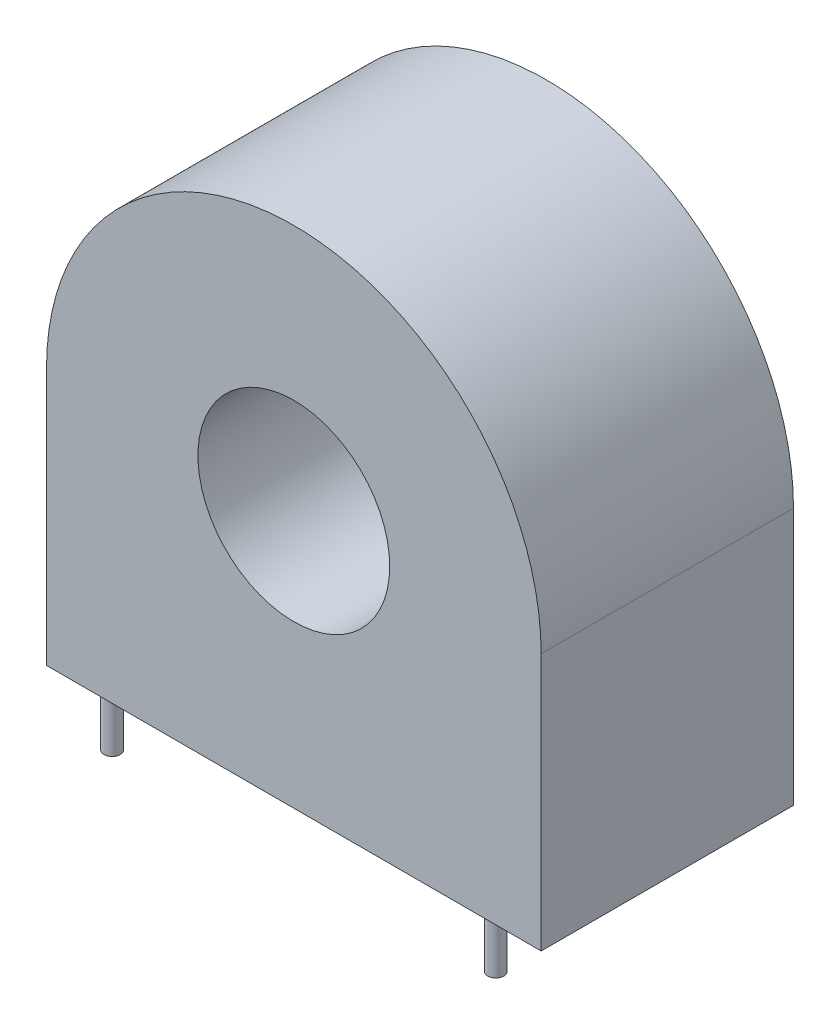
SolidWorks part; units mm, degrees
ref_plane "Front" through (0, 0, 0) normal (0, 0, 1) x (1, 0, 0)
ref_plane "Top" through (0, 0, 0) normal (0, 1, 0) x (1, 0, 0)
ref_plane "Right" through (0, 0, 0) normal (1, 0, 0) x (0, 0, -1)
sketch "Эскиз1" plane through (0, 0, 0) normal (0, 0, 1) x (1, 0, 0)
  line L1 (12.25, -6.375) -> (-12.25, -6.375)
  line L2 (12.25, -6.375) -> (12.25, 6.375)
  line L3 (12.25, 6.375) -> (-12.25, 6.375) construction
  line L4 (-12.25, -6.375) -> (-12.25, 6.375)
  line L5 (12.25, -6.375) -> (-12.25, 6.375) construction
  line L6 (12.25, 6.375) -> (-12.25, -6.375) construction
  arc A0 (12.25, 6.375) -> (-12.25, 6.375) centre (0, 6.375) ccw
  circle A1 centre (0, 6.375) radius 4.75
  point P0 (0, 0)
  dimension "D3" = 9.5
  dimension "D1" = 24.5
  dimension "D2" = 12.75
extrude "Бобышка-Вытянуть1" add sketch "Эскиз1" along normal blind 12.5
sketch "Эскиз2" plane through (0, -6.375, 0) normal (0, -1, 0) x (1, 0, 0)
  line L0 (0, -1000) -> (0, 49000) construction
  line L1 (-12.25, 0) -> (12.25, 0) construction
  line L3 (7.4, 0.5) -> (-7.4, 0.5) construction
  line L4 (9.5, 12) -> (-9.5, 12) construction
  line L5 (-12.25, 12.5) -> (12.25, 12.5) construction
  circle A0 centre (7.4, 0.5) radius 0.4
  circle A1 centre (-7.4, 0.5) radius 0.4
  circle A2 centre (9.5, 12) radius 0.4
  circle A3 centre (-9.5, 12) radius 0.4
  point P7 (0, 0)
  point P9 (0, 0.5)
  point P14 (0, 12)
  dimension "D2" = 0.8
  dimension "D1" = 0.5
  dimension "D3" = 14.8
  dimension "D4" = 19
  dimension "D5" = 0.5
extrude "Бобышка-Вытянуть2" add sketch "Эскиз2" along normal blind 2.5
ref_axis "Ось1" through (0, 6.375, 12.5) along (0, 0, -1)
